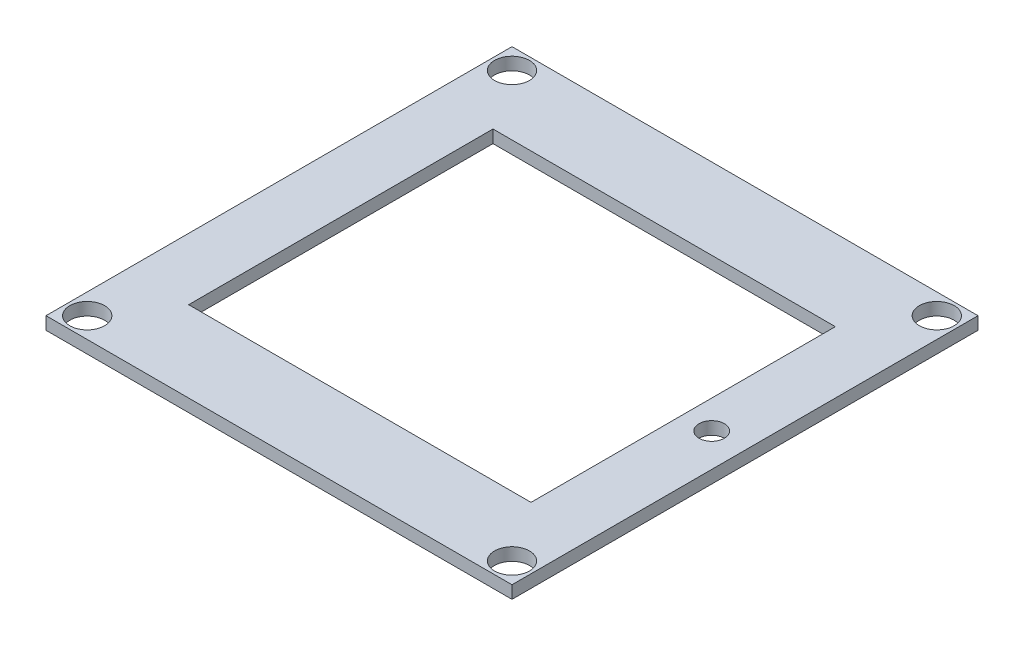
SolidWorks part; units mm, degrees
ref_plane "Front Plane" through (0, 0, 0) normal (0, 0, 1) x (1, 0, 0)
ref_plane "Top Plane" through (0, 0, 0) normal (0, 1, 0) x (1, 0, 0)
ref_plane "Right Plane" through (0, 0, 0) normal (1, 0, 0) x (0, 0, -1)
sketch "Sketch1" plane through (0, 0, 0) normal (0, 1, 0) x (1, 0, 0)
  line L0 (147, 147) -> (147, -147)
  line L1 (-147, -147) -> (147, -147)
  line L2 (-147, -147) -> (-147, 147)
  line L3 (-147, 147) -> (147, 147)
  line L5 (-147, -147) -> (147, 147) construction
  line L6 (-147, 147) -> (147, -147) construction
  line L7 (-108, -96) -> (108, -96)
  line L8 (-108, -96) -> (-108, 96)
  line L9 (-108, 96) -> (108, 96)
  line L10 (108, -96) -> (108, 96)
  line L11 (-108, -96) -> (108, 96) construction
  line L12 (-108, 96) -> (108, -96) construction
  point P0 (0, 0)
  point P5 (0, 0)
  dimension "D1" = 294
  dimension "D2" = 216
  dimension "D3" = 192
extrude "Boss-Extrude1" add sketch "Sketch1" along normal blind 8
sketch "Sketch2" plane through (0, 0, 0) normal (0, 1, 0) x (1, 0, 0)
  line L1 (147, 147) -> (-147, 147) construction
  line L2 (147, -147) -> (147, 147) construction
  circle A0 centre (134, 134) radius 11
  dimension "D1" = 22
  dimension "D2" = 13
  dimension "D3" = 13
extrude "Cut-Extrude1" cut sketch "Sketch2" along normal through all
sketch "Sketch4" plane through (0, 8, 0) normal (0, 1, 0) x (1, 0, 0)
  line L0 (134, -864) -> (134, 49136) construction
  circle A0 centre (126, 0) radius 8
  dimension "D1" = 8
  dimension "D2" = 16
mirror "Mirror2" about plane through (0, 0, 0) normal (0, 0, 1) of "Cut-Extrude1"
extrude "Cut-Extrude2" cut sketch "Sketch4" against normal through all
mirror "Mirror3" about plane through (0, 0, 0) normal (1, 0, 0) of "Mirror2", "Cut-Extrude1"
